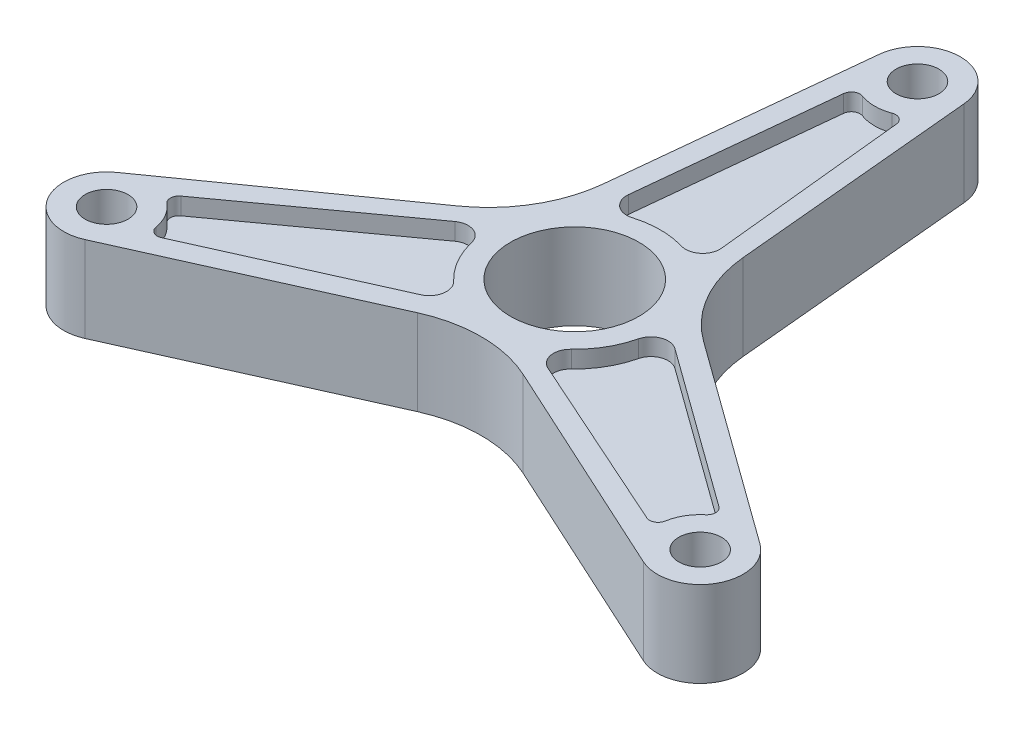
SolidWorks part; units mm, degrees
ref_plane "Piano frontale" through (0, 0, 0) normal (0, 0, 1) x (1, 0, 0)
ref_plane "Piano superiore" through (0, 0, 0) normal (0, 1, 0) x (1, 0, 0)
ref_plane "Piano destro" through (0, 0, 0) normal (1, 0, 0) x (0, 0, -1)
sketch "Schizzo1" plane through (0, 0, 0) normal (0, 1, 0) x (1, 0, 0)
  line L0 (0, 0) -> (0, 113.5406) construction
  line L1 (-9.9476, 81.0227) -> (-15.9535, 22.6022)
  line L2 (-5.8594, 71.8965) -> (-11.5739, 16.3109)
  line L3 (5.8594, 71.8965) -> (11.5739, 16.3109)
  line L4 (9.9569, 80.928) -> (15.2586, 24.0417)
  line L5 (75.1415, -31.8965) -> (27.5508, 2.515)
  line L6 (65.1072, -49.0869) -> (13.1914, -25.2352)
  line L7 (65.1939, -30.8738) -> (19.9126, 1.8679)
  line L8 (59.3345, -41.0227) -> (8.3387, -18.1787)
  line L9 (0, 0) -> (98.3291, -56.7703) construction
  line L10 (-65.1939, -49.1262) -> (-11.5973, -25.1172)
  line L11 (-75.0641, -31.8411) -> (-28.45, 1.1935)
  line L12 (-59.3345, -41.0227) -> (-8.3387, -18.1787)
  line L13 (-65.1939, -30.8738) -> (-19.9126, 1.8679)
  line L14 (0, 0) -> (-98.3291, -56.7703) construction
  circle A0 centre (0, 0) radius 15
  circle A1 centre (0, 80) radius 5
  circle A3 centre (0, 0) radius 22.5 construction
  arc A4 (8.3387, -18.1787) -> (19.9126, 1.8679) centre (0, 0) ccw
  arc A5 (-15.9535, 22.6022) -> (-28.45, 1.1935) centre (-45.7962, 25.6702) cw
  arc A6 (-5.8594, 71.8965) -> (5.8594, 71.8965) centre (0, 80) ccw
  circle A7 centre (69.282, -40) radius 5
  arc A8 (65.1939, -30.8738) -> (59.3345, -41.0227) centre (69.282, -40) ccw
  arc A9 (27.5508, 2.515) -> (15.2586, 24.0417) centre (45.1291, 26.8256) cw
  circle A10 centre (-69.282, -40) radius 5
  arc A11 (-59.3345, -41.0227) -> (-65.1939, -30.8738) centre (-69.282, -40) ccw
  arc A12 (-11.5973, -25.1172) -> (13.1914, -25.2352) centre (0.6671, -52.4958) cw
  arc A13 (9.9569, 80.928) -> (-9.9476, 81.0227) centre (0, 80) ccw
  arc A14 (65.1072, -49.0869) -> (75.1415, -31.8965) centre (69.282, -40) ccw
  arc A15 (-75.0641, -31.8411) -> (-65.1939, -49.1262) centre (-69.282, -40) ccw
  arc A16 (11.5739, 16.3109) -> (-11.5739, 16.3109) centre (0, 0) ccw
  arc A17 (-19.9126, 1.8679) -> (-8.3387, -18.1787) centre (0, 0) ccw
  point P3 (0, 0)
  point P28 (0, 0)
  point P29 (0, 0)
  point P42 (0, 0)
  point P43 (0, 0)
  point P45 (0, 0)
  point P46 (0, 0)
  point P47 (0, 0)
  point P49 (0, 0)
  point P50 (0, 0)
  point P51 (0, 0)
  point P52 (0, 0)
  point P53 (0, 0)
  point P54 (0, 0)
  point P57 (0, 0)
  point P58 (0, 0)
  point P59 (0, 0)
  dimension "D1" = 30
  dimension "D2" = 10
  dimension "D3" = 20
  dimension "D5" = 45
  dimension "D6" = 40
  dimension "D7" = 30
  dimension "D4" = 80
  dimension "D8" = 3
  dimension "D9" = 120
  dimension "D10" = 5
  dimension "D11" = 3
extrude "Estrusione-Estrusione3" add sketch "Schizzo1" along normal mid plane 20
extrude "Estrusione-Estrusione4" add sketch "Schizzo1<2>" along normal mid plane 12 contours A17 L13 A11 L12 | A16 L3 A6 L2 | A8 L7 A4 L8 region at (0, 0, -42.0677) region at (36.4317, 0, 21.0339) region at (-36.4317, 0, 21.0339)
sketch "Schizzo1<2>" plane through (0, 0, 0) normal (0, 1, 0) x (1, 0, 0) same geometry as "Schizzo1"
fillet "Raccordo1" radius 2 12 edges at (-59.3345, -8, 41.0227) (-65.1939, -8, 30.8738) (-59.3345, 8, 41.0227) (-65.1939, 8, 30.8738) (65.1939, 8, 30.8738) (59.3345, 8, 41.0227) (59.3345, -8, 41.0227) (65.1939, -8, 30.8738) (-5.8594, -8, -71.8965) (-5.8594, 8, -71.8965) (5.8594, 8, -71.8965) (5.8594, -8, -71.8965)
fillet "Raccordo2" radius 4 12 edges at (-19.9126, -8, -1.8679) (-11.5739, -8, -16.3109) (11.5739, -8, -16.3109) (-8.3387, -8, 18.1787) (19.9126, -8, -1.8679) (8.3387, -8, 18.1787) (-11.5739, 8, -16.3109) (-8.3387, 8, 18.1787) (-19.9126, 8, -1.8679) (8.3387, 8, 18.1787) (19.9126, 8, -1.8679) (11.5739, 8, -16.3109)
sketch "Schizzo2" plane through (0, 10, 0) normal (0, 1, 0) x (1, 0, 0)
  line L0 (0, 0) -> (0, 110.9504) construction
